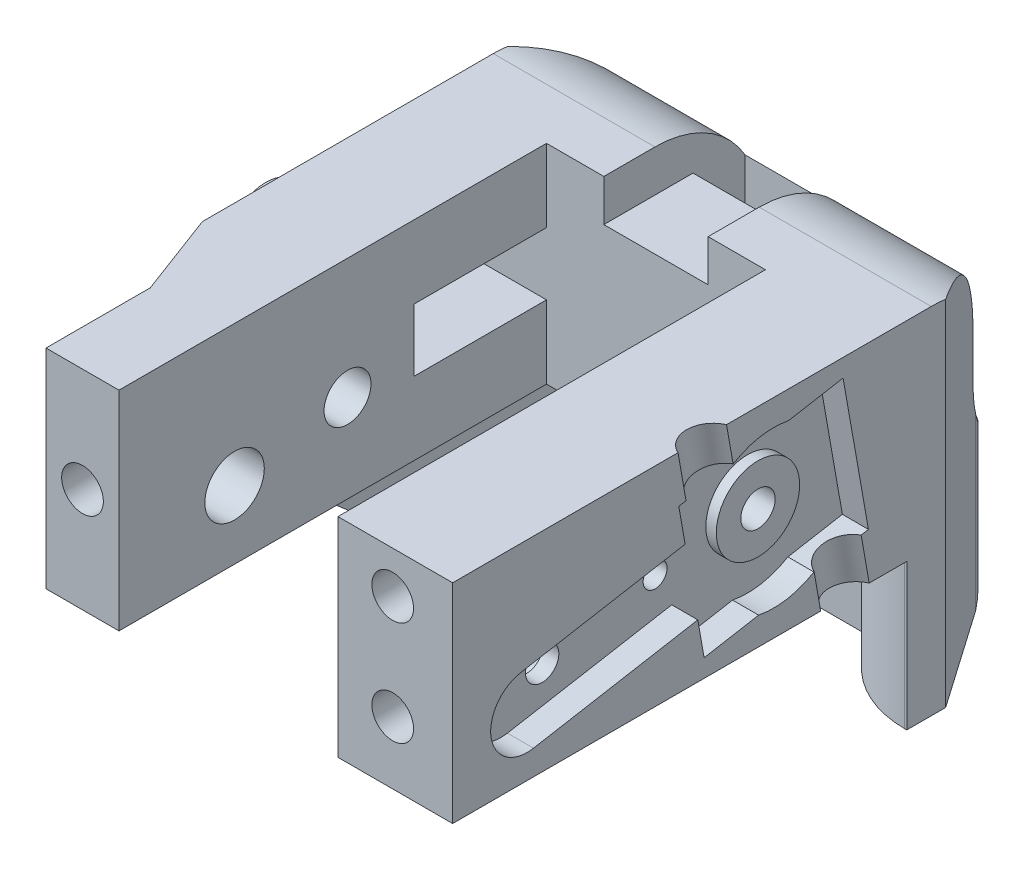
SolidWorks part; units mm, degrees
material "ABS"
ref_plane "Front Plane" through (0, 0, 0) normal (0, 0, 1) x (1, 0, 0)
ref_plane "Top Plane" through (0, 0, 0) normal (0, 1, 0) x (1, 0, 0)
ref_plane "Right Plane" through (0, 0, 0) normal (1, 0, 0) x (0, 0, -1)
sketch "Sketch1" plane through (0, 0, 0) normal (0, 1, 0) x (1, 0, 0)
  line L0 (-15.5, -37) -> (-10, -37)
  line L2 (-15.5, -37) -> (-15.5, 10)
  line L3 (-15.5, 10) -> (21, 10)
  line L4 (21, -19) -> (21, 10)
  line L5 (-10, -37) -> (-10, 4)
  line L6 (-10, 4) -> (11, 4)
  line L7 (11, 4) -> (11, -37)
  line L9 (21, -19) -> (18, -27)
  line L10 (18, -27) -> (18, -37)
  line L11 (11, -37) -> (18, -37)
  point P0 (0, 0)
  dimension "D1" = 36.5
  dimension "D2" = 7
  dimension "D3" = 21
  dimension "D4" = 10
  dimension "D5" = 21
  dimension "D6" = 41
  dimension "D7" = 47
  dimension "D8" = 8
  dimension "D9" = 5.5
  dimension "D10" = 10
extrude "Boss-Extrude1" add sketch "Sketch1" along normal blind 20
sketch "Sketch6" plane through (-15.5, 0, 0) normal (-1, 0, 0) x (0, 0, 1)
  line L1 (15, 0) -> (-10, 0)
  line L2 (15, 0) -> (15, 20)
  line L3 (15, 20) -> (-10, 20)
  line L4 (-10, 0) -> (-10, 20)
  line L5 (-10, 20) -> (-10, 0) construction
  line L7 (-10, 0) -> (37, 0) construction
  line L8 (-10, 20) -> (37, 20) construction
  dimension "D3" = 25
extrude "Boss-Extrude5" add sketch "Sketch6" along normal blind 5.5
sketch "Sketch20" plane through (0, 20, 0) normal (0, 1, 0) x (1, 0, 0)
  line L4 (-21, 6.5542) -> (13, 6.5542)
  line L11 (21.0063, -11.8234) -> (21.0063, 10.2821)
  line L12 (21.0063, 10.2821) -> (15.0032, 18.9016)
  line L13 (15.0032, 18.9016) -> (-14.9968, 18.9016)
  line L14 (-14.9968, 18.9016) -> (-21, 10.2821)
  line L15 (-21, 10) -> (-21, -15) construction
  line L16 (-21, 10.2821) -> (-21, 6.5542)
  line L18 (13, 6.5542) -> (13, -16.4458)
  line L20 (13, -16.4458) -> (21.0063, -11.8234)
  dimension "D2" = 23
  dimension "D4" = 30
  dimension "D8" = 34
  dimension "D9" = 60
  dimension "D1" = 6.0032
  dimension "D3" = 6.0032
  dimension "D5" = 8.6195
  dimension "D6" = 8.6195
  dimension "D7" = 3.7279
extrude "Boss-Extrude11" add sketch "Sketch20" along normal blind 14 and the other way up to surface (20 mm away) other way up to face at (0.5833, 0, 16.3333)
sketch "Sketch4" plane through (0, 20, 0) normal (0, 1, 0) x (1, 0, 0)
  line L2 (-10, 4) -> (11, 4) construction
  line L4 (-10, -37) -> (-10, 4) construction
  circle A6 centre (-4.375, 8) radius 2
  circle A7 centre (5.375, 8) radius 2
  dimension "D1" = 4
  dimension "D2" = 4
  dimension "D3" = 9.75
  dimension "D4" = 5.625
extrude "Cut-Extrude1" cut sketch "Sketch4" against normal blind 10
sketch "Sketch24" plane through (0, 34, 0) normal (0, 1, 0) x (1, 0, 0)
  line L0 (21.0063, 10.2821) -> (15.0032, 18.9016) construction
  line L1 (-14.9968, 18.9016) -> (-14.4209, 19.7285)
  line L2 (-21, 10.2821) -> (-21, 6.5542) construction
  line L3 (-14.9968, 18.9016) -> (-21, 10.2821) construction
  line L4 (21.0063, 10.2821) -> (15.0032, 18.9016)
  line L6 (-21, 10.2821) -> (-21, 6.5542)
  line L7 (-14.9968, 18.9016) -> (-21, 10.2821)
  line L11 (-21, 6.5542) -> (13, 6.5542) construction
  line L14 (-21, 6.5542) -> (21.0063, 6.5542)
  line L16 (21.0063, 10.2821) -> (21.0063, 6.5542)
  line L17 (21.0063, -11.8234) -> (21.0063, 10.2821) construction
  arc A3 (8.6131, 24.6437) -> (-14.4209, 19.7285) centre (-0.0555, 8.8374) ccw
  arc A4 (8.6131, 24.6437) -> (15.0032, 18.9016) centre (-0.4313, 8.152) cw
  dimension "D3" = 18.0273
  dimension "D4" = 18.8089
  dimension "D1" = 0.5759
  dimension "D2" = 1.0077
extrude "Boss-Extrude13" add sketch "Sketch24" against normal blind 12
fillet "Fillet11" radius 7.95 1 edges at (0.0032, 22, -18.9016)
chamfer "Chamfer1" distance 14 angle 45 1 edges at (17.0032, 34, 14.1346)
sketch "Sketch26" plane through (-21, 0, 0) normal (-1, 0, 0) x (0, 0, 1)
  line L0 (15, 0) -> (37, 0)
  line L2 (37, 0) -> (37, 20)
  line L3 (37, 20) -> (15, 20)
  line L4 (15, 0) -> (15, 20) construction
  line L5 (15, 20) -> (15, 0)
extrude "Boss-Extrude14" add sketch "Sketch26" against normal up to surface (11 mm away) up to face at (-10, 10, 16.5)
sketch "Sketch25" plane through (-21, 0, 0) normal (-1, 0, 0) x (0, 0, 1)
  line L0 (12.1426, 14.5987) -> (29.2456, 17.6144)
  line L1 (13.3582, 7.705) -> (30.4611, 10.7207)
  line L2 (30.4611, 10.7207) -> (29.2456, 17.6144) construction
  line L3 (6.2179, 10) -> (29.8533, 14.1676) construction
  line L4 (-10.2821, 0) -> (37, 0) construction
  line L5 (6.2179, 10) -> (6.2179, 38.8588) construction
  line L7 (-10.2821, 34) -> (-10.2821, 0) construction
  arc A1 (12.1426, 14.5987) -> (13.3582, 7.705) centre (6.2179, 10) ccw
  arc A3 (29.2456, 17.6144) -> (30.4611, 10.7207) centre (29.8533, 14.1676) cw
  dimension "D1" = 7.5
  dimension "D2" = 7
  dimension "D3" = 24
  dimension "D4" = 7
  dimension "D5" = 80
  dimension "D6" = 16.5
  dimension "D7" = 10
extrude "Cut-Extrude7" cut sketch "Sketch25" against normal blind 2.5
sketch "Sketch27" plane through (-18.5, 0, 0) normal (-1, 0, 0) x (0, 0, 1)
  line L0 (6.2179, 10) -> (29.8533, 14.1676) construction
  circle A0 centre (6.2179, 10) radius 4
  circle A1 centre (15.0812, 11.5628) radius 1.15
  circle A4 centre (25.9141, 13.473) radius 1.6
  dimension "D1" = 8
  dimension "D3" = 2.3
  dimension "D4" = 3.2
  dimension "D2" = 9
  dimension "D5" = 4
extrude "Cut-Extrude8" cut sketch "Sketch27" against normal up to next
sketch "Sketch28" plane through (-21, 0, 0) normal (-1, 0, 0) x (0, 0, 1)
  line L0 (-2.8761, 15.5045) -> (12.8809, 18.2828)
  line L1 (12.8809, 18.2828) -> (15.3119, 4.4955)
  line L2 (15.3119, 4.4955) -> (-0.445, 1.7172)
  line L3 (-0.445, 1.7172) -> (-2.8761, 15.5045)
  line L6 (29.2456, 17.6144) -> (12.1426, 14.5987) construction
  circle A0 centre (6.2179, 10) radius 4 construction
  dimension "D1" = 8
  dimension "D2" = 7
  dimension "D3" = 14
  dimension "D4" = 16
extrude "Cut-Extrude9" cut sketch "Sketch28" against normal blind 2.5
sketch "Sketch29" plane through (0, 15.5288, -2.7381) normal (0, -0.9848, 0.1736) x (1, 0, 0)
  line L0 (-18.5, 5.1674) -> (-18.5, -0.14) construction
  line L3 (-21, 10.5525) -> (-21, 5.1674) construction
  circle A0 centre (-22, 2.86) radius 2.5
  point P6 (-21, 7.86)
  dimension "D1" = 5
  dimension "D2" = 3.5
  dimension "D3" = 5
extrude "Cut-Extrude10" cut sketch "Sketch29" against normal up to next
sketch "Sketch30" plane through (0, 1.7415, -0.3071) normal (0, 0.9848, -0.1736) x (1, 0, 0)
  line L0 (-21, -10.5525) -> (-21, -15.86) construction
  line L1 (-21, -5.1674) -> (-21, -10.5525) construction
  circle A0 centre (-22, -12.86) radius 2.5
  point P6 (-21, -7.86)
  dimension "D1" = 5
  dimension "D2" = 1
  dimension "D3" = 5
extrude "Cut-Extrude11" cut sketch "Sketch30" against normal up to next
sketch "Sketch31" plane through (-18.5, 0, 0) normal (-1, 0, 0) x (0, 0, 1)
  circle A0 centre (6.2179, 10) radius 4
  circle A1 centre (6.2179, 10) radius 1.65
  dimension "D1" = 8
  dimension "D2" = 3.3
extrude "Boss-Extrude15" add sketch "Sketch31" along normal blind 1 and the other way blind 2
sketch "Sketch32" plane through (-10, 0, 0) normal (1, 0, 0) x (0, 0, -1)
  circle A0 centre (-25.9141, 13.473) radius 2.85
  circle A3 centre (-15.0812, 11.5628) radius 2.25
  dimension "D1" = 5.7
  dimension "D2" = 4.5
extrude "Cut-Extrude12" cut sketch "Sketch32" against normal blind 7 and the other way up to next
sketch "Sketch33" plane through (21.0063, 0, 0) normal (1, 0, 0) x (0, 0, -1)
  circle A0 centre (-6.2179, 10) radius 3.8
  circle A1 centre (-6.2179, 10) radius 1.65 construction
  dimension "D1" = 7.6
extrude "Boss-Extrude17" add sketch "Sketch33" along normal blind 7
fillet "Fillet17" radius 1 1 edges at (28.0063, 10, 2.4179)
sketch "Sketch35" plane through (0, 34, 0) normal (0, 1, 0) x (1, 0, 0)
  line L0 (-21, 6.5542) -> (13, 6.5542) construction
  line L1 (-20.8, 6.5542) -> (13, 6.5542)
  line L3 (-10.8027, 12.5542) -> (13, 12.5542)
  line L4 (13, 6.5542) -> (13, 12.5542)
  line L7 (13, 6.5542) -> (13, -0.28) construction
  arc A0 (-20.8, 6.5542) -> (-13.285, 9.9568) centre (-20.8, 16.5542) ccw
  arc A1 (-13.285, 9.9568) -> (-10.8027, 12.5542) centre (18.6614, -18.0889) cw
  dimension "D3" = 42.5104
  dimension "D4" = 10
  dimension "D5" = 8.2494
  dimension "D1" = 23.8027
  dimension "D2" = 6
  dimension "D6" = 9.9972
extrude "Cut-Extrude13" cut sketch "Sketch35" against normal up to surface (14 mm away) up to face at (1.4167, 20, 9.7117)
sketch "Sketch36" plane through (0, 0, 37) normal (0, 0, 1) x (1, 0, 0)
  line L0 (11, 20) -> (11, 0) construction
  line L1 (11, 20) -> (18, 20) construction
  line L2 (-21, 0) -> (-21, 20) construction
  line L6 (-21, 20) -> (-10, 20) construction
  circle A0 centre (-15.25, 14) radius 2
  circle A1 centre (14.5, 10) radius 2
  circle A2 centre (-15.25, 4) radius 2
  dimension "D3" = 4
  dimension "D1" = 5.75
  dimension "D2" = 3.5
  dimension "D4" = 10
  dimension "D5" = 6
  dimension "D6" = 5.75
  dimension "D7" = 10
extrude "Cut-Extrude14" cut sketch "Sketch36" against normal blind 10
fillet "Fillet18" radius 10 1 edges at (0.0032, 0, -18.9016)
sketch "Sketch37" plane through (21, 0, 0) normal (1, 0, 0) x (0, 0, -1)
  line L0 (-6.2179, 10) -> (6.304, 10) construction
  line L1 (4, 20) -> (4, 0) construction
  line L2 (-1.7179, 13) -> (4, 13)
  line L3 (-1.7179, 13) -> (-1.7179, 7)
  line L4 (-1.7179, 7) -> (4, 7)
  line L5 (4, 13) -> (4, 7)
  point P7 (0.043, 10)
  dimension "D1" = 6
  dimension "D2" = 3
  dimension "D4" = 4.5
extrude "Cut-Extrude16" cut sketch "Sketch37" against normal up to next
chamfer "Chamfer2" distance 7 angle 45 1 edges at (11, 10, 1.7179)
sketch "Sketch38" plane through (0, 0, 0) normal (0, -1, 0) x (1, 0, 0)
  line L0 (-10, -4) -> (11, -4) construction
  line L1 (-4.5, -4) -> (5.5, -4)
  line L2 (-4.5, -4) -> (-4.5, -24)
  line L3 (-4.5, -24) -> (5.5, -24)
  line L4 (5.5, -4) -> (5.5, -24)
  line L5 (-10, 37) -> (-10, -4) construction
  dimension "D1" = 10
  dimension "D2" = 5.5
  dimension "D3" = 20
extrude "Cut-Extrude17" cut sketch "Sketch38" against normal blind 4
sketch "Sketch39" plane through (0, 34, 0) normal (0, 1, 0) x (1, 0, 0)
  line L0 (13, 12.5542) -> (-10.8027, 12.5542) construction
  line L1 (-4.5, 12.5542) -> (5.5, 12.5542)
  line L2 (-4.5, 12.5542) -> (-4.5, 17.5542)
  line L3 (-4.5, 17.5542) -> (5.5, 17.5542)
  line L4 (5.5, 12.5542) -> (5.5, 17.5542)
  line L5 (5.5, 16.9016) -> (5.5, 4) construction
  line L6 (-4.5, 4) -> (-4.5, 16.9016) construction
  dimension "D1" = 5
extrude "Cut-Extrude19" cut sketch "Sketch39" against normal up to next
ref_plane "Plane1" through (-31, 0, 0) normal (-1, 0, 0) x (0, 0, 1)
mirror "Mirror1" about plane through (-31, 0, 0) normal (-1, 0, 0) of bodies 140
sketch "Sketch40" plane through (0, 0, -18.9016) normal (0, 0, -1) x (-1, 0, 0)
  line L1 (-37.1576, -4.2201) -> (26.4203, -4.2201)
  line L2 (-37.1576, -4.2201) -> (-37.1576, 81.1631)
  line L3 (-37.1576, 81.1631) -> (26.4203, 81.1631)
  line L4 (26.4203, -4.2201) -> (26.4203, 81.1631)
extrude "Cut-Extrude20" cut sketch "Sketch40" against normal through all both and the other way through all
sketch "Sketch41" plane through (0, 34, 0) normal (0, 1, 0) x (1, 0, 0)
  circle A0 centre (-67.1107, 22.5147) radius 2
  circle A1 centre (-77.9107, 11.6065) radius 2
  dimension "D1" = 4
  dimension "D2" = 10.8
  dimension "D3" = 10.9081
  dimension "D4" = 5.0956
  dimension "D5" = 1.3245
extrude "Cut-Extrude21" cut sketch "Sketch41" against normal blind 8
ref_plane "Plane2" through (0, -10, 0) normal (0, -1, 0) x (-1, 0, 0)
mirror "Mirror2" about plane through (0, -10, 0) normal (0, -1, 0) of bodies 142
sketch "Sketch42" plane through (0, 0, -18.9016) normal (0, 0, -1) x (-1, 0, 0)
  line L1 (96.3546, 55.7837) -> (12.1577, 55.7837)
  line L2 (96.3546, 55.7837) -> (96.3546, -11.9439)
  line L3 (96.3546, -11.9439) -> (12.1577, -11.9439)
  line L4 (12.1577, 55.7837) -> (12.1577, -11.9439)
extrude "Cut-Extrude22" cut sketch "Sketch42" against normal through all both and the other way through all
equation "\"D4@Sketch4\"=(21-\"D3@Sketch4\")/2"
equation "\"D2@Sketch37\"=\"D1@Sketch37\"/2"
equation "\"D3@Sketch20\"=\"D1@Sketch20\""
equation "\"D6@Sketch20\"=\"D5@Sketch20\""
